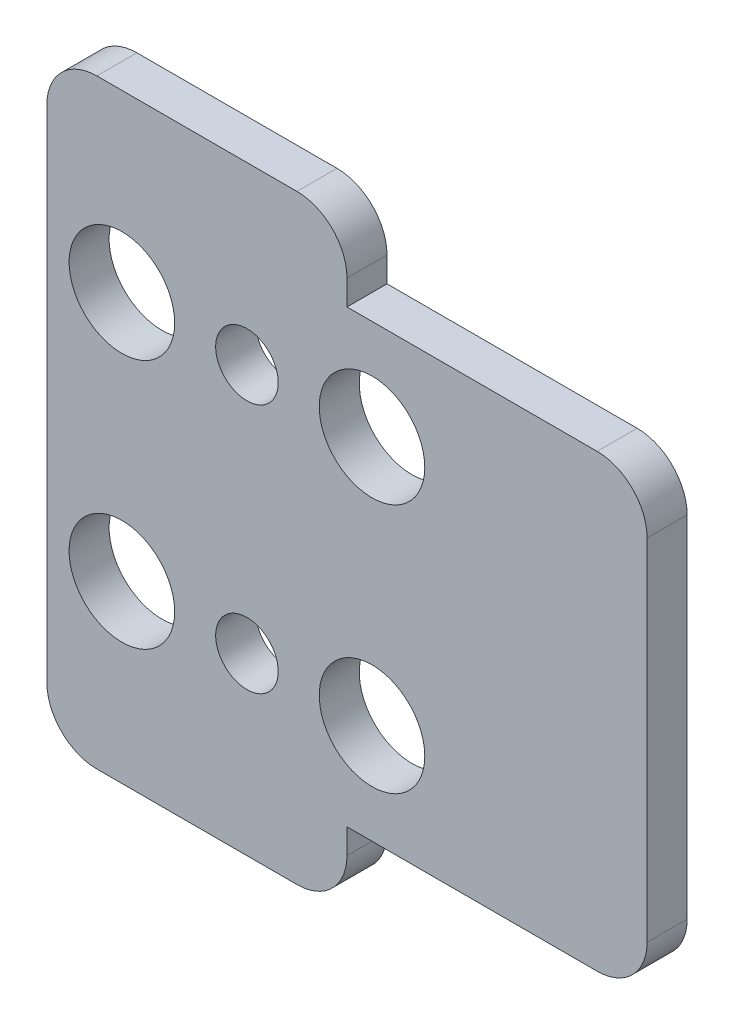
SolidWorks part; units mm, degrees
ref_plane "前视基准面" through (0, 0, 0) normal (0, 0, 1) x (1, 0, 0)
ref_plane "上视基准面" through (0, 0, 0) normal (0, 1, 0) x (1, 0, 0)
ref_plane "右视基准面" through (0, 0, 0) normal (1, 0, 0) x (0, 0, -1)
sketch "草图1" plane through (0, 0, 0) normal (0, 0, 1) x (1, 0, 0)
  line L0 (-378.0337, -12) -> (18431.0563, -12) construction
  line L1 (0, 0) -> (12, 0)
  line L2 (0, 0) -> (0, -24)
  line L3 (0, -24) -> (12, -24)
  line L4 (12, 0) -> (12, -24)
  line L6 (24, -3) -> (12, -3)
  line L7 (24, -3) -> (24, -21)
  line L8 (24, -21) -> (12, -21)
  line L9 (12, -3) -> (12, -21)
  line L10 (24, -3) -> (12, -21) construction
  line L11 (24, -21) -> (12, -3) construction
  circle A0 centre (3, -7) radius 2.11
  circle A1 centre (8, -7) radius 1.25
  circle A3 centre (13, -7) radius 2.11
  circle A4 centre (13, -17) radius 2.11
  circle A5 centre (8, -17) radius 1.25
  circle A6 centre (3, -17) radius 2.11
  point P8 (0, -12)
  point P9 (18, -12)
  dimension "D8" = 4.22
  dimension "D9" = 2.5
  dimension "D10" = 4.22
  dimension "D1" = 12
  dimension "D2" = 12
  dimension "D3" = 3
  dimension "D4" = 24
  dimension "D5" = 3
  dimension "D6" = 5
  dimension "D7" = 5
  dimension "D11" = 5
  dimension "D12" = 0
  dimension "D13" = 0
extrude "凸台-拉伸1" add sketch "草图1" along normal blind 1.6 contours L4 A4 A3 L1 L2 L3 A5 A1 A0 A6 | L4 A4 L8 L7 L6 A3 region at (6.1298, -12, 0) region at (18.5258, -12, 0)
fillet "圆角1" radius 2 6 edges at (0, -24, 0.8) (12, -24, 0.8) (24, -21, 0.8) (24, -3, 0.8) (12, 0, 0.8) (0, 0, 0.8)
